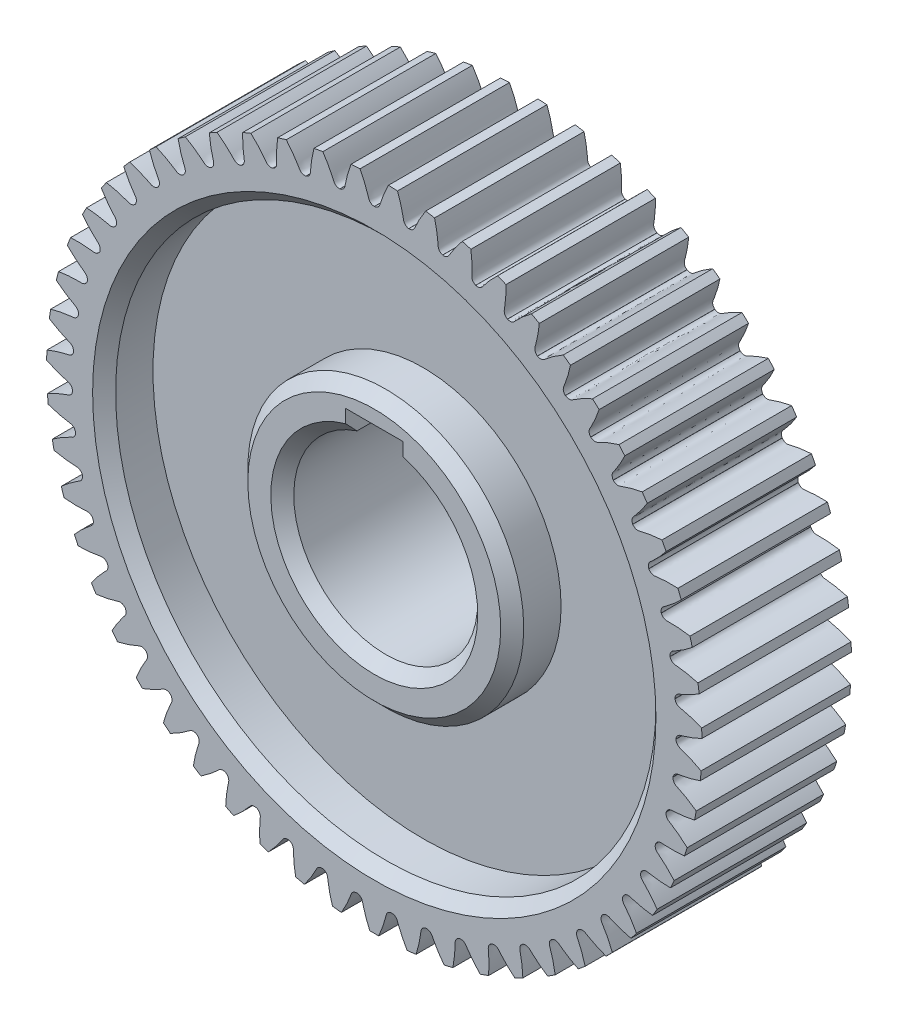
SolidWorks part; units mm, degrees
material "45"
ref_plane "前视基准面" through (0, 0, 0) normal (0, 0, 1) x (1, 0, 0)
ref_plane "上视基准面" through (0, 0, 0) normal (0, 1, 0) x (1, 0, 0)
ref_plane "右视基准面" through (0, 0, 0) normal (1, 0, 0) x (0, 0, -1)
sketch "草图1" plane through (0, 0, 0) normal (0, 0, 1) x (1, 0, 0)
  circle A0 centre (0, 0) radius 57
extrude "凸台-拉伸1" add sketch "草图1" along normal blind 26
ref_axis "基准轴1" through (0, 0, 26) along (0, 0, -1)
sketch "草图2" plane through (0, 0, 0) normal (0, 0, 1) x (1, 0, 0)
  line L0 (0, 0) -> (0, 57) construction
  circle A0 centre (0, 0) radius 57 construction
  arc A1 (0.01, 52.5) -> (-0.01, 52.5) centre (0, 0) ccw
  arc A2 (8.1241, 64.5295) -> (-8.1241, 64.5295) centre (0, 0) ccw
  spline S0 degree 3 poles (0.01, 52.5) (0.8611, 52.6123) (0.982, 53.2782) (1.2185, 54.0107) (1.3227, 54.3181) (1.4404, 54.6426) (1.572, 54.984) (1.7182, 55.3419) (1.8797, 55.7157) (2.0573, 56.105) (2.2515, 56.5094) (2.4631, 56.9282) (2.6928, 57.361) (2.941, 57.8071) (3.2086, 58.2661) (3.4961, 58.7373) (3.804, 59.2201) (4.133, 59.7138) (4.4836, 60.2178) (4.8563, 60.7315) (5.2518, 61.254) (5.6704, 61.7848) (6.1126, 62.3231) (6.579, 62.8682) (7.2427, 63.6132) (7.7644, 64.1642) (8.1241, 64.5295) knots 0 0 0 0 0.114641 0.135337 0.157442 0.180954 0.205875 0.232203 0.25994 0.289085 0.319639 0.3516 0.38497 0.419747 0.455933 0.493527 0.532529 0.57294 0.614758 0.657985 0.70262 0.748663 0.796114 0.844973 0.895241 1 1 1 1
  spline S1 degree 3 poles (-0.01, 52.5) (-0.8611, 52.6123) (-0.982, 53.2782) (-1.2185, 54.0107) (-1.3227, 54.3181) (-1.4404, 54.6426) (-1.572, 54.984) (-1.7182, 55.3419) (-1.8797, 55.7157) (-2.0573, 56.105) (-2.2515, 56.5094) (-2.4631, 56.9282) (-2.6928, 57.361) (-2.941, 57.8071) (-3.2086, 58.2661) (-3.4961, 58.7373) (-3.804, 59.2201) (-4.133, 59.7138) (-4.4836, 60.2178) (-4.8563, 60.7315) (-5.2518, 61.254) (-5.6704, 61.7848) (-6.1126, 62.3231) (-6.579, 62.8682) (-7.2427, 63.6132) (-7.7644, 64.1642) (-8.1241, 64.5295) knots 0 0 0 0 0.114641 0.135337 0.157442 0.180954 0.205875 0.232203 0.25994 0.289085 0.319639 0.3516 0.38497 0.419747 0.455933 0.493527 0.532529 0.57294 0.614758 0.657985 0.70262 0.748663 0.796114 0.844973 0.895241 1 1 1 1
extrude "切除-拉伸1" cut sketch "草图2" along normal through all
pattern_circular "阵列(圆周)1" count 55 every 6.545 about axis through (0, 0, 26) along (0, 0, -1) of "切除-拉伸1"
sketch "草图3" plane through (0, 0, 0) normal (0, 0, 1) x (1, 0, 0)
  circle A0 centre (0, 0) radius 55 construction
  dimension "Dn" = 110
sketch "草图4" plane through (0, 0, 26) normal (0, 0, 1) x (1, 0, 0)
  line L0 (-5, 19.6) -> (5, 19.6)
  line L1 (5, 19.6) -> (5, 15.1987)
  line L2 (-5, 19.6) -> (-5, 15.1987)
  arc A0 (-5, 15.1987) -> (5, 15.1987) centre (0, 0) ccw
  point P5 (0, 19.6)
  dimension "D1" = 32
  dimension "D2" = 10
  dimension "D3" = 19.6
extrude "切除-拉伸2" cut sketch "草图4" against normal through all both and the other way through all
chamfer "倒角1" distance 2 angle 45 1 edges at (0, -16, 26)
sketch "草图5" plane through (0, 0, 0) normal (0, 1, 0) x (1, 0, 0)
  line L0 (0, 32.0911) -> (0, 78.3888) construction
  line L1 (-47, 4.607) -> (-47, -8.5)
  line L2 (-47, -8.5) -> (-24, -8.5)
  line L3 (-24, -8.5) -> (-24, 4.607)
  line L4 (-24, 4.607) -> (-47, 4.607)
  line L5 (-56.9491, 0) -> (-56.9491, -26) construction
  line L6 (-56.9491, -13) -> (-10.4881, -13) construction
  line L7 (-10.4881, -26) -> (-10.4881, 0) construction
  line L8 (-24, -30.607) -> (-47, -30.607)
  line L9 (-24, -17.5) -> (-24, -30.607)
  line L10 (-47, -17.5) -> (-24, -17.5)
  line L11 (-47, -30.607) -> (-47, -17.5)
  dimension "D1" = 94
  dimension "D2" = 48
  dimension "D3" = 9
revolve "切除-旋转1" cut sketch "草图5" angle 360 about L0
chamfer "倒角2" distance 2 angle 45 4 edges at (24, 0, 26) (47, 0, 26) (24, 0, 0) (47, 0, 0)
chamfer "倒角3" distance 2 angle 45 1 edges at (0, -16, 0)
